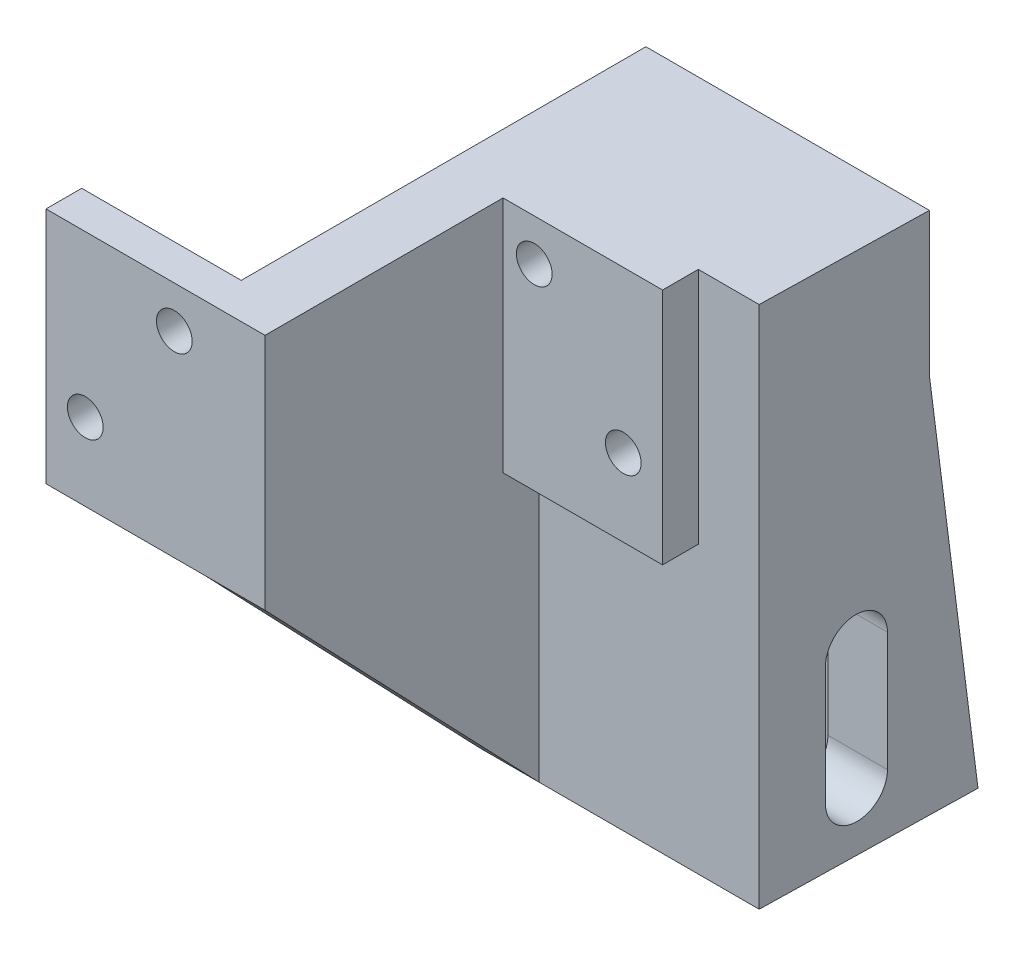
SolidWorks part; units mm, degrees
ref_plane "Front Plane" through (0, 0, 0) normal (0, 0, 1) x (1, 0, 0)
ref_plane "Top Plane" through (0, 0, 0) normal (0, 1, 0) x (1, 0, 0)
ref_plane "Right Plane" through (0, 0, 0) normal (1, 0, 0) x (0, 0, -1)
sketch "Sketch1" plane through (0, 0, 0) normal (0, 1, 0) x (1, 0, 0)
  line L0 (0, 0) -> (18.4, 0)
  line L1 (18.4, 0) -> (18.4, 20)
  line L2 (18.4, 20) -> (31.8, 20)
  line L3 (31.8, 20) -> (31.8, 23)
  line L4 (31.8, 23) -> (13.4, 23)
  line L5 (13.4, 23) -> (13.4, 3)
  line L6 (13.4, 3) -> (0, 3)
  line L7 (0, 3) -> (0, 0)
  dimension "D1" = 13.4
  dimension "D2" = 5
  dimension "D3" = 3
  dimension "D4" = 17
extrude "Boss-Extrude1" add sketch "Sketch1" along normal blind 20
sketch "Sketch2" plane through (0, 0, -20) normal (0, 0, 1) x (1, 0, 0)
  line L1 (31.8, 20) -> (31.8, 0) construction
  line L2 (31.8, 0) -> (13.4, 0) construction
  circle A0 centre (28.5, 6.5) radius 1.5
  circle A1 centre (21.02, 16.5) radius 1.5
  dimension "D1" = 3
  dimension "D2" = 6.5
  dimension "D3" = 3.3
  dimension "D4" = 10.78
  dimension "D5" = 16.5
extrude "Cut-Extrude1" cut sketch "Sketch2" against normal through all both and the other way through all
ref_plane "Plane1" through (15.9, 0, 0) normal (-1, 0, 0) x (0, 0, 1)
mirror "Mirror1" about plane through (15.9, 0, 0) normal (-1, 0, 0) of "Cut-Extrude1"
sketch "Sketch3" plane through (13.4, 0, 0) normal (-1, 0, 0) x (0, 0, 1)
  line L0 (-23, 0) -> (-23, -24)
  line L1 (-23, -24) -> (-41, -24)
  line L2 (-41, -24) -> (-37, 8)
  line L3 (-37, 8) -> (-37, 20)
  line L4 (-37, 20) -> (-23, 20)
  line L5 (-23, 20) -> (-23, 0)
  line L6 (-23, 0) -> (-3, 0) construction
  line L7 (-31, -19) -> (-31, -9) construction
  line L8 (-33.55, -19) -> (-33.55, -9)
  line L9 (-28.45, -19) -> (-28.45, -9)
  arc A0 (-33.55, -19) -> (-28.45, -19) centre (-31, -19) ccw
  arc A1 (-28.45, -9) -> (-33.55, -9) centre (-31, -9) ccw
  point P12 (-31, -14)
  point P17 (-31.0407, -18.5371)
  dimension "D1" = 18
  dimension "D2" = 14
  dimension "D3" = 12
  dimension "D4" = 24
  dimension "D5" = 5.1
  dimension "D6" = 10
  dimension "D7" = 5
  dimension "D8" = 8
extrude "Boss-Extrude2" add sketch "Sketch3" against normal offset from surface (23.9 mm away) 5.5 up to face at (31.8, 10, -21.5) offset beyond the face yes
sketch "Sketch4" plane through (0, 0, -23) normal (0, 0, 1) x (1, 0, 0)
  circle A0 centre (28.5, 6.5) radius 3
  circle A1 centre (21.02, 16.5) radius 3
  dimension "D1" = 6
extrude "Cut-Extrude2" cut sketch "Sketch4" against normal through all
sketch "Sketch5" plane through (13.4, 0, 0) normal (-1, 0, 0) x (0, 0, 1)
  line L0 (0, 0) -> (-23, -24)
  line L1 (-23, -24) -> (-23, 0)
  line L2 (-23, 0) -> (0, 0)
  point P4 (0, 0)
extrude "Boss-Extrude3" add sketch "Sketch5" against normal up to surface (5 mm away) up to face at (18.4, 10, -10)
sketch "Sketch8" plane through (0, -24, 0) normal (0, -1, 0) x (1, 0, 0)
  line L0 (37.3, -41) -> (36.9167, -23)
  line L1 (37.3, -23) -> (18.4, -23) construction
  line L2 (36.9167, -23) -> (37.3, -23)
  line L3 (37.3, -23) -> (37.3, -41)
  dimension "D1" = 1.22
extrude "Cut-Extrude3" cut sketch "Sketch8" against normal through all
sketch "Sketch9" plane through (13.4, 0, 0) normal (-1, 0, 0) x (0, 0, 1)
  line L0 (-37, -9) -> (-37, -24)
  line L3 (-25, -9) -> (-25, -24)
  line L4 (-41, -24) -> (-23, -24) construction
  line L5 (-37, -24) -> (-25, -24)
  arc A4 (-37, -9) -> (-25, -9) centre (-31, -9) cw
  arc A5 (-28.45, -9) -> (-33.55, -9) centre (-31, -9) ccw construction
  dimension "D1" = 6
extrude "Cut-Extrude4" cut sketch "Sketch9" against normal offset from surface (18.8137 mm away) 5 up to face at (37.1126, 0, -32.2)
